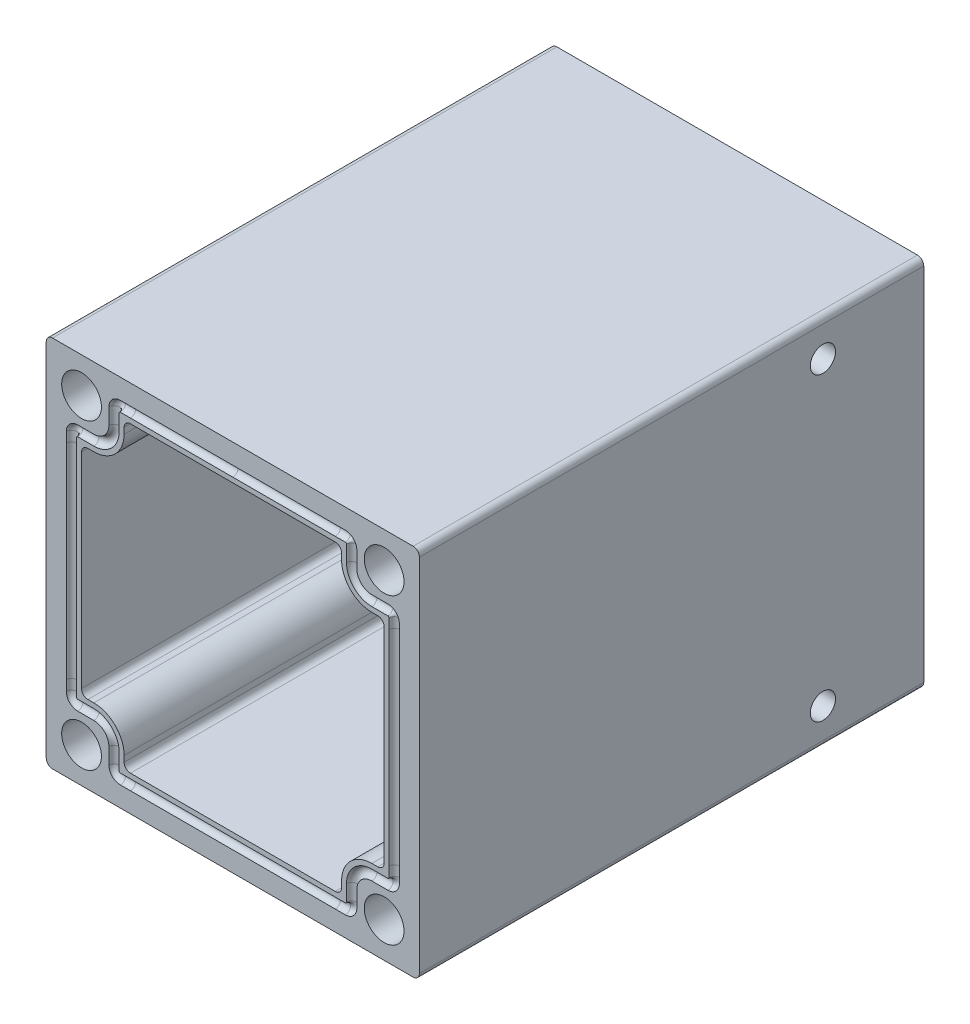
SolidWorks part; units mm, degrees
material "1060 Alloy"
ref_plane "Front Plane" through (0, 0, 0) normal (0, 0, 1) x (1, 0, 0)
ref_plane "Top Plane" through (0, 0, 0) normal (0, 1, 0) x (1, 0, 0)
ref_plane "Right Plane" through (0, 0, 0) normal (1, 0, 0) x (0, 0, -1)
sketch "Sketch1" plane through (0, 0, 0) normal (0, 0, 1) x (1, 0, 0)
  line L9 (23.495, 22.7012) -> (23.495, -22.7012)
  line L14 (22.7012, -23.495) -> (-22.7012, -23.495)
  line L15 (-23.495, -22.7012) -> (-23.495, 22.7012)
  line L16 (-22.7012, 23.495) -> (22.7012, 23.495)
  line L28 (-20.32, -12.8968) -> (-20.32, -14.1668) construction
  line L34 (-14.1669, -20.32) -> (-12.8969, -20.32) construction
  line L51 (-12.8969, -20.32) -> (12.8968, -20.32) construction
  line L54 (20.32, -12.8969) -> (20.32, 12.8968) construction
  line L57 (12.8969, 20.32) -> (-12.8968, 20.32) construction
  line L60 (-20.32, 12.8969) -> (-20.32, -12.8968) construction
  line L63 (-19.5262, -14.9606) -> (-17.5006, -14.9606) construction
  line L64 (-12.8969, -19.05) -> (12.8968, -19.05)
  line L65 (-13.6906, 18.2563) -> (-13.6906, 17.5006)
  line L66 (-17.5006, 13.6906) -> (-18.2562, 13.6906)
  line L67 (18.2563, 13.6906) -> (17.5006, 13.6906)
  line L68 (13.6906, 17.5006) -> (13.6906, 18.2562)
  line L69 (13.6906, -18.2563) -> (13.6906, -17.5006)
  line L70 (17.5006, -13.6906) -> (18.2562, -13.6906)
  line L71 (-14.9606, -17.5006) -> (-14.9606, -19.5262) construction
  line L73 (-12.8968, 20.32) -> (-14.1668, 20.32) construction
  line L74 (-14.9606, 19.5262) -> (-14.9606, 17.5006) construction
  line L75 (-17.5006, 14.9606) -> (-19.5262, 14.9606) construction
  line L76 (-20.32, 14.1669) -> (-20.32, 12.8969) construction
  line L77 (20.32, 12.8968) -> (20.32, 14.1668) construction
  line L78 (19.5263, 14.9606) -> (17.5006, 14.9606) construction
  line L79 (14.9606, 17.5006) -> (14.9606, 19.5262) construction
  line L80 (14.1669, 20.32) -> (12.8969, 20.32) construction
  line L81 (12.8968, -20.32) -> (14.1668, -20.32) construction
  line L82 (14.9606, -19.5263) -> (14.9606, -17.5006) construction
  line L83 (17.5006, -14.9606) -> (19.5262, -14.9606) construction
  line L84 (20.32, -14.1669) -> (20.32, -12.8969) construction
  line L85 (-18.2563, -13.6906) -> (-17.5006, -13.6906)
  line L86 (-13.6906, -17.5006) -> (-13.6906, -18.2562)
  line L90 (19.05, -12.8969) -> (19.05, 12.8968)
  line L93 (12.8969, 19.05) -> (-12.8968, 19.05)
  line L97 (-19.05, 12.8969) -> (-19.05, -12.8968)
  circle A0 centre (0, 0) radius 19.05 construction
  circle A13 centre (-19.05, -19.05) radius 2.5019 construction
  circle A14 centre (-19.05, 19.05) radius 2.5019 construction
  circle A15 centre (19.05, 19.05) radius 2.5019 construction
  circle A16 centre (19.05, -19.05) radius 2.5019 construction
  circle A17 centre (19.05, -19.05) radius 4.0894 construction
  arc A50 (-13.6906, -17.5006) -> (-17.5006, -13.6906) centre (-17.5006, -17.5006) ccw
  arc A51 (-12.8969, -19.05) -> (-13.6906, -18.2562) centre (-12.8969, -18.2562) cw
  arc A52 (-18.2563, -13.6906) -> (-19.05, -12.8968) centre (-18.2563, -12.8968) cw
  arc A53 (-13.6906, 18.2563) -> (-12.8968, 19.05) centre (-12.8968, 18.2563) cw
  arc A54 (-17.5006, 13.6906) -> (-13.6906, 17.5006) centre (-17.5006, 17.5006) ccw
  arc A55 (-19.05, 12.8969) -> (-18.2562, 13.6906) centre (-18.2562, 12.8969) cw
  arc A56 (18.2563, 13.6906) -> (19.05, 12.8968) centre (18.2563, 12.8968) cw
  arc A57 (13.6906, 17.5006) -> (17.5006, 13.6906) centre (17.5006, 17.5006) ccw
  arc A58 (12.8969, 19.05) -> (13.6906, 18.2562) centre (12.8969, 18.2562) cw
  arc A59 (13.6906, -18.2563) -> (12.8968, -19.05) centre (12.8968, -18.2563) cw
  arc A60 (17.5006, -13.6906) -> (13.6906, -17.5006) centre (17.5006, -17.5006) ccw
  arc A61 (19.05, -12.8969) -> (18.2562, -13.6906) centre (18.2562, -12.8969) cw
  arc A62 (-14.9606, -17.5006) -> (-17.5006, -14.9606) centre (-17.5006, -17.5006) ccw construction
  arc A63 (-14.1669, -20.32) -> (-14.9606, -19.5262) centre (-14.1669, -19.5262) cw construction
  arc A64 (-20.32, -14.1668) -> (-19.5262, -14.9606) centre (-19.5262, -14.1668) ccw construction
  arc A65 (-14.1668, 20.32) -> (-14.9606, 19.5262) centre (-14.1668, 19.5262) ccw construction
  arc A66 (-17.5006, 14.9606) -> (-14.9606, 17.5006) centre (-17.5006, 17.5006) ccw construction
  arc A67 (-20.32, 14.1669) -> (-19.5262, 14.9606) centre (-19.5262, 14.1669) cw construction
  arc A68 (20.32, 14.1668) -> (19.5263, 14.9606) centre (19.5263, 14.1668) ccw construction
  arc A69 (14.9606, 17.5006) -> (17.5006, 14.9606) centre (17.5006, 17.5006) ccw construction
  arc A70 (14.1669, 20.32) -> (14.9606, 19.5262) centre (14.1669, 19.5262) cw construction
  arc A71 (14.1668, -20.32) -> (14.9606, -19.5263) centre (14.1668, -19.5263) ccw construction
  arc A72 (17.5006, -14.9606) -> (14.9606, -17.5006) centre (17.5006, -17.5006) ccw construction
  arc A73 (20.32, -14.1669) -> (19.5262, -14.9606) centre (19.5262, -14.1669) cw construction
  arc A74 (-22.7012, -23.495) -> (-23.495, -22.7012) centre (-22.7013, -22.7013) cw
  arc A75 (22.7012, -23.495) -> (23.495, -22.7012) centre (22.7012, -22.7012) ccw
  arc A76 (23.495, 22.7012) -> (22.7012, 23.495) centre (22.7012, 22.7013) ccw
  arc A77 (-23.495, 22.7012) -> (-22.7012, 23.495) centre (-22.7013, 22.7012) cw
  point P29 (0, 0)
  point P32 (0, 0)
  point P33 (0, 0)
  point P42 (0, 0)
  point P45 (19.05, -14.9606)
  point P57 (14.9606, -19.05)
  point P82 (0, 0)
  point P89 (0, 0)
  point P140 (0, 0)
  dimension "D1" = 38.1
  dimension "D2" = 3.175
  dimension "D3" = 3.175
  dimension "D5" = 4
  dimension "D6" = 1.5875
  dimension "D8" = 5.0038
  dimension "D9" = 0.7937
  dimension "D7" = 3.81
  dimension "D4" = 2.54
  dimension "D14" = 0.7937
  dimension "D11" = 0.7937
  dimension "D12" = 3.175
  dimension "D13" = 3.175
  dimension "D15" = 4
  dimension "D10" = 4
extrude "Boss-Extrude1" add sketch "Sketch1" against normal blind 63.5 contours A17 A16 | L16 L15 L14 L9 L84 A73 L83 A72 L82 A71 L81 L51 L34 A63 L71 A62 L63 A64 L28 L60 L76 A67 L75 A66 L74 A65 L73 L57 L80 A70 L79 A69 L78 A68 L77 L54 | A73 L84 L54 L77 A68 L78 A69 L79 A70 L80 L57 L73 A65 L74 A66 L75 A67 L76 L60 L28 A64 L63 A62 L71 A63 L34 L51 L81 A71 L82 A72 L83 region at (22.8305, 0, 0)
sketch "Sketch4" [suppressed] plane through (0, 0, 0) normal (1, 0, 0) x (0, 0, -1)
  line L0 (0, 38.1462) -> (65.278, 38.1462) construction
  line L3 (0, 0) -> (65.278, 0) construction
  line L5 (0, -29.86) -> (65.278, -29.86) construction
  line L6 (0, 52.7974) -> (0, 23.495) construction
  line L7 (65.278, 52.7974) -> (65.278, 23.495) construction
  line L8 (0, -36.225) -> (0, -23.495) construction
  line L9 (65.278, -36.225) -> (65.278, -23.495) construction
  line L10 (65.278, -23.495) -> (65.278, 23.495) construction
  circle A0 centre (12.7, 38.1306) radius 3.9688
  circle A1 centre (52.578, 38.1306) radius 3.9687
  circle A2 centre (10.6423, -36.7905) radius 3.9688
  circle A3 centre (54.6357, -36.7905) radius 3.9687
  dimension "D1" = 12.7
  dimension "D3" = 7.9375
  dimension "D4" = 7.9375
  dimension "D2" = 12.7
  dimension "D5" = 12.7
  dimension "D6" = 12.7
extrude "Cut-Extrude2" [suppressed] cut sketch "Sketch4" along normal through all contours A1 | A0 | A3 | A2
sketch "Sketch7" plane through (0, 0, 0) normal (1, 0, 0) x (0, 0, -1)
  circle A0 centre (0, 20.32) radius 0.65
  dimension "D1" = 1.3
sketch "Sketch11" plane through (0, 0, 0) normal (0, 0, 1) x (1, 0, 0)
  line L0 (-14.9606, 19.5262) -> (-14.9606, 17.5006) construction
  line L1 (-12.8968, 20.32) -> (-14.1668, 20.32) construction
  line L2 (12.8969, 20.32) -> (-12.8968, 20.32) construction
  line L3 (14.1669, 20.32) -> (12.8969, 20.32) construction
  line L4 (14.9606, 17.5006) -> (14.9606, 19.5262) construction
  line L5 (19.5263, 14.9606) -> (17.5006, 14.9606) construction
  line L6 (20.32, 12.8968) -> (20.32, 14.1668) construction
  line L7 (20.32, -12.8969) -> (20.32, 12.8968) construction
  line L8 (20.32, -14.1669) -> (20.32, -12.8969) construction
  line L9 (17.5006, -14.9606) -> (19.5262, -14.9606) construction
  line L10 (14.9606, -19.5263) -> (14.9606, -17.5006) construction
  line L11 (12.8968, -20.32) -> (14.1668, -20.32) construction
  line L12 (-12.8969, -20.32) -> (12.8968, -20.32) construction
  line L13 (-14.1669, -20.32) -> (-12.8969, -20.32) construction
  line L14 (-14.9606, -17.5006) -> (-14.9606, -19.5262) construction
  line L15 (-19.5262, -14.9606) -> (-17.5006, -14.9606) construction
  line L16 (-20.32, -12.8968) -> (-20.32, -14.1668) construction
  line L17 (-20.32, 12.8969) -> (-20.32, -12.8968) construction
  line L18 (-20.32, 14.1669) -> (-20.32, 12.8969) construction
  line L19 (-17.5006, 14.9606) -> (-19.5262, 14.9606) construction
  line L20 (-14.9606, 19.5262) -> (-14.9606, 17.5006)
  line L21 (-12.8968, 20.32) -> (-14.1668, 20.32)
  line L22 (12.8969, 20.32) -> (-12.8968, 20.32)
  line L23 (14.1669, 20.32) -> (12.8969, 20.32)
  line L24 (14.9606, 17.5006) -> (14.9606, 19.5262)
  line L25 (19.5263, 14.9606) -> (17.5006, 14.9606)
  line L26 (20.32, 12.8968) -> (20.32, 14.1668)
  line L27 (20.32, -12.8969) -> (20.32, 12.8968)
  line L28 (20.32, -14.1669) -> (20.32, -12.8969)
  line L29 (17.5006, -14.9606) -> (19.5262, -14.9606)
  line L30 (14.9606, -19.5263) -> (14.9606, -17.5006)
  line L31 (12.8968, -20.32) -> (14.1668, -20.32)
  line L32 (-12.8969, -20.32) -> (12.8968, -20.32)
  line L33 (-14.1669, -20.32) -> (-12.8969, -20.32)
  line L34 (-14.9606, -17.5006) -> (-14.9606, -19.5262)
  line L35 (-19.5262, -14.9606) -> (-17.5006, -14.9606)
  line L36 (-20.32, -12.8968) -> (-20.32, -14.1668)
  line L37 (-20.32, 12.8969) -> (-20.32, -12.8968)
  line L38 (-20.32, 14.1669) -> (-20.32, 12.8969)
  line L39 (-17.5006, 14.9606) -> (-19.5262, 14.9606)
  arc A0 (-14.1668, 20.32) -> (-14.9606, 19.5262) centre (-14.1668, 19.5262) ccw construction
  arc A1 (14.9606, 19.5262) -> (14.1669, 20.32) centre (14.1669, 19.5262) ccw construction
  arc A2 (14.9606, 17.5006) -> (17.5006, 14.9606) centre (17.5006, 17.5006) ccw construction
  arc A3 (20.32, 14.1668) -> (19.5263, 14.9606) centre (19.5263, 14.1668) ccw construction
  arc A4 (19.5262, -14.9606) -> (20.32, -14.1669) centre (19.5262, -14.1669) ccw construction
  arc A5 (17.5006, -14.9606) -> (14.9606, -17.5006) centre (17.5006, -17.5006) ccw construction
  arc A6 (14.1668, -20.32) -> (14.9606, -19.5263) centre (14.1668, -19.5263) ccw construction
  arc A7 (-14.9606, -19.5262) -> (-14.1669, -20.32) centre (-14.1669, -19.5262) ccw construction
  arc A8 (-14.9606, -17.5006) -> (-17.5006, -14.9606) centre (-17.5006, -17.5006) ccw construction
  arc A9 (-20.32, -14.1668) -> (-19.5262, -14.9606) centre (-19.5262, -14.1668) ccw construction
  arc A10 (-19.5262, 14.9606) -> (-20.32, 14.1669) centre (-19.5262, 14.1669) ccw construction
  arc A11 (-17.5006, 14.9606) -> (-14.9606, 17.5006) centre (-17.5006, 17.5006) ccw construction
  arc A12 (-14.1668, 20.32) -> (-14.9606, 19.5262) centre (-14.1668, 19.5262) ccw
  arc A13 (14.9606, 19.5262) -> (14.1669, 20.32) centre (14.1669, 19.5262) ccw
  arc A14 (14.9606, 17.5006) -> (17.5006, 14.9606) centre (17.5006, 17.5006) ccw
  arc A15 (20.32, 14.1668) -> (19.5263, 14.9606) centre (19.5263, 14.1668) ccw
  arc A16 (19.5262, -14.9606) -> (20.32, -14.1669) centre (19.5262, -14.1669) ccw
  arc A17 (17.5006, -14.9606) -> (14.9606, -17.5006) centre (17.5006, -17.5006) ccw
  arc A18 (14.1668, -20.32) -> (14.9606, -19.5263) centre (14.1668, -19.5263) ccw
  arc A19 (-14.9606, -19.5262) -> (-14.1669, -20.32) centre (-14.1669, -19.5262) ccw
  arc A20 (-14.9606, -17.5006) -> (-17.5006, -14.9606) centre (-17.5006, -17.5006) ccw
  arc A21 (-20.32, -14.1668) -> (-19.5262, -14.9606) centre (-19.5262, -14.1668) ccw
  arc A22 (-19.5262, 14.9606) -> (-20.32, 14.1669) centre (-19.5262, 14.1669) ccw
  arc A23 (-17.5006, 14.9606) -> (-14.9606, 17.5006) centre (-17.5006, 17.5006) ccw
sweep "Cut-Sweep2" cut profiles "Sketch7" path "Sketch11"
sketch "Sketch10" plane through (0, 0, 0) normal (0, 0, 1) x (1, 0, 0)
  circle A0 centre (19.05, 19.05) radius 2.5019 construction
  circle A1 centre (19.05, -19.05) radius 2.5019 construction
  circle A2 centre (-19.05, -19.05) radius 2.5019 construction
  circle A3 centre (-19.05, 19.05) radius 2.5019 construction
  circle A4 centre (19.05, 19.05) radius 2.5019
  circle A5 centre (19.05, -19.05) radius 2.5019
  circle A6 centre (-19.05, -19.05) radius 2.5019
  circle A7 centre (-19.05, 19.05) radius 2.5019
extrude "Cut-Extrude3" cut sketch "Sketch10" against normal blind 12.7
sketch "Sketch12" plane through (0, 0, 0) normal (0, 0, 1) x (1, 0, 0)
  line L0 (23.495, 22.7012) -> (23.495, -22.7012) construction
  line L1 (22.7012, -23.495) -> (-22.7012, -23.495) construction
  line L2 (-23.495, -22.7012) -> (-23.495, 22.7012) construction
  line L3 (-22.7012, 23.495) -> (22.7012, 23.495) construction
  line L4 (23.495, 22.7012) -> (23.495, -22.7012)
  line L5 (22.7012, -23.495) -> (-22.7012, -23.495)
  line L6 (-23.495, -22.7012) -> (-23.495, 22.7012)
  line L7 (-22.7012, 23.495) -> (22.7012, 23.495)
  arc A0 (23.495, 22.7012) -> (22.7012, 23.495) centre (22.7012, 22.7013) ccw construction
  arc A1 (22.7012, -23.495) -> (23.495, -22.7012) centre (22.7012, -22.7012) ccw construction
  arc A2 (-23.495, -22.7012) -> (-22.7012, -23.495) centre (-22.7013, -22.7013) ccw construction
  arc A3 (-22.7012, 23.495) -> (-23.495, 22.7012) centre (-22.7013, 22.7012) ccw construction
  arc A4 (23.495, 22.7012) -> (22.7012, 23.495) centre (22.7012, 22.7013) ccw
  arc A5 (22.7012, -23.495) -> (23.495, -22.7012) centre (22.7012, -22.7012) ccw
  arc A6 (-23.495, -22.7012) -> (-22.7012, -23.495) centre (-22.7013, -22.7013) ccw
  arc A7 (-22.7012, 23.495) -> (-23.495, 22.7012) centre (-22.7013, 22.7012) ccw
  circle A8 centre (0, 0) radius 10.414
  dimension "D1" = 20.828
extrude "Boss-Extrude2" add sketch "Sketch12" along normal blind 3.175 from surface starting at face at (0, 0, -63.5)
sketch "Sketch13" plane through (23.495, 0, 0) normal (1, 0, 0) x (0, 0, -1)
  line L0 (0, 0) -> (63.5, 0)
  line L1 (0, 22.7012) -> (0, -22.7012) construction
  line L2 (63.5, 22.7012) -> (63.5, -22.7012) construction
  line L3 (31.75, 22.7012) -> (31.75, -22.7012)
  line L4 (63.5, 22.7012) -> (0, 22.7012) construction
  line L5 (63.5, -22.7012) -> (0, -22.7012) construction
sketch "Sketch14" plane through (23.495, 0, 0) normal (1, 0, 0) x (0, 0, -1)
  line L0 (63.5, 22.7012) -> (63.5, -22.7012) construction
  line L1 (63.5, 23.495) -> (0, 23.495) construction
  line L2 (63.5, -23.495) -> (0, -23.495) construction
  circle A0 centre (50.8, 18.923) radius 1.5875
  circle A1 centre (50.8, -18.923) radius 1.5875
  dimension "D3" = 3.175
  dimension "D4" = 3.175
  dimension "D1" = 12.7
  dimension "D2" = 12.7
  dimension "D5" = 4.572
  dimension "D6" = 4.572
extrude "Cut-Extrude4" cut sketch "Sketch14" against normal blind 6.35
